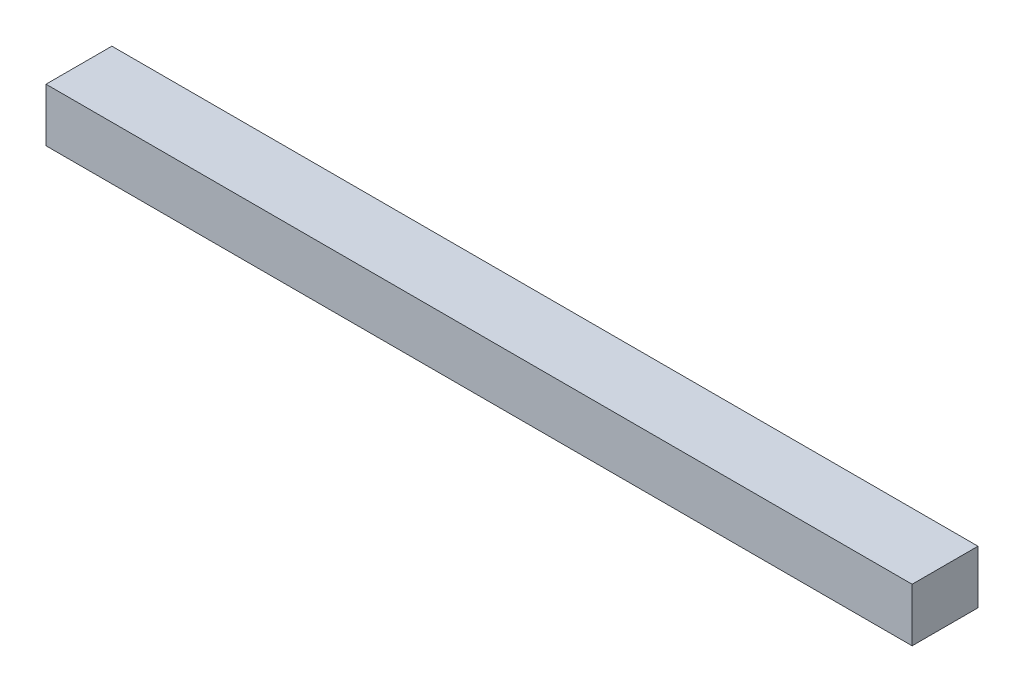
SolidWorks part; units mm, degrees
ref_plane "Спереди" through (0, 0, 0) normal (0, 0, 1) x (1, 0, 0)
ref_plane "Сверху" through (0, 0, 0) normal (0, 1, 0) x (1, 0, 0)
ref_plane "Справа" through (0, 0, 0) normal (1, 0, 0) x (0, 0, -1)
sketch "Эскиз1" plane through (0, 0, 0) normal (0, 1, 0) x (1, 0, 0)
  text T0 "RuCtf: a99c5731f33f5350f52a6213dd21687e"
sketch "Эскиз2" plane through (0, 0, 0) normal (0, 1, 0) x (1, 0, 0)
  line L1 (0, 5.5062) -> (111.6329, 5.5062)
  line L2 (0, 5.5062) -> (0, -1.1369)
  line L3 (0, -1.1369) -> (111.6329, -1.1369)
  line L4 (111.6329, 5.5062) -> (111.6329, -1.1369)
extrude "Вытянуть-Тонкостенный1" add sketch "Эскиз2" along normal blind 5.5 and the other way blind 0.5 thin thin type one direction wall 1
sketch "Эскиз3" plane through (0, -0.5, 0) normal (0, -1, 0) x (1, 0, 0)
  line L1 (112.6329, 2.1369) -> (-1, 2.1369)
  line L2 (112.6329, 2.1369) -> (112.6329, -6.5062)
  line L3 (112.6329, -6.5062) -> (-1, -6.5062)
  line L4 (-1, 2.1369) -> (-1, -6.5062)
extrude "Бобышка-Вытянуть3" add sketch "Эскиз3" along normal blind 0.5
extrude "Бобышка-Вытянуть4" add sketch "Эскиз1" along normal blind 4.5 separate body
sketch "Эскиз4" plane through (0, 5.5, 0) normal (0, 1, 0) x (1, 0, 0)
  line L1 (-1, 6.5062) -> (112.6329, 6.5062)
  line L2 (-1, 6.5062) -> (-1, -2.1369)
  line L3 (-1, -2.1369) -> (112.6329, -2.1369)
  line L4 (112.6329, 6.5062) -> (112.6329, -2.1369)
extrude "Бобышка-Вытянуть5" add sketch "Эскиз4" along normal blind 0.5
